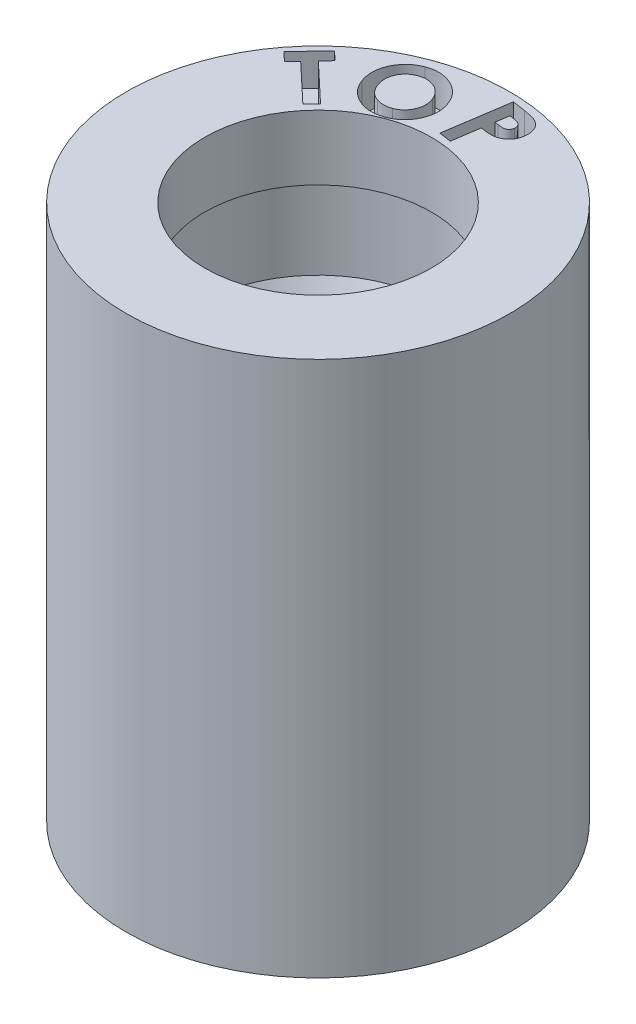
SolidWorks part; units mm, degrees
ref_plane "Front Plane" through (0, 0, 0) normal (0, 0, 1) x (1, 0, 0)
ref_plane "Top Plane" through (0, 0, 0) normal (0, 1, 0) x (1, 0, 0)
ref_plane "Right Plane" through (0, 0, 0) normal (1, 0, 0) x (0, 0, -1)
sketch "Sketch1" plane through (0, 0, 0) normal (0, 0, 1) x (1, 0, 0)
  line L0 (-5.9256, 16.5395) -> (-5.9256, 0)
  line L1 (-5.9256, 0) -> (-2.5, 0)
  line L2 (-2.5, 0) -> (-2.5, 1)
  line L3 (-2.5, 1) -> (-4.9256, 1) construction
  line L4 (-4.9256, 1) -> (-4.9256, 4) construction
  line L5 (-4.9256, 4) -> (-2.1655, 1.2398) construction
  line L6 (-2.1655, 1.2398) -> (-4.9256, 6.9535) construction
  line L7 (-4.9256, 6.9535) -> (-4.9256, 7.9535) construction
  line L8 (-4.9256, 7.9535) -> (-2.2655, 5.2933) construction
  line L9 (-2.2655, 5.2933) -> (-4.9256, 10.8) construction
  line L10 (-4.9256, 10.8) -> (-4.9256, 11.8) construction
  line L11 (-4.9256, 11.8) -> (-2.3655, 9.2398) construction
  line L12 (-4.9256, 7.9535) -> (-4.9256, 10.8) construction
  line L13 (-4.9256, 4) -> (-4.9256, 6.9535) construction
  line L14 (-2.3655, 9.2398) -> (-4.9256, 14.5395) construction
  line L15 (-4.9256, 14.5395) -> (-4.9256, 16.5395) construction
  line L16 (-3.1, 2.1744) -> (-3.1, 3.1744)
  line L17 (-3.2, 6.2279) -> (-3.2, 7.2279)
  line L18 (-3.3, 10.1744) -> (-3.3, 11.1744)
  line L19 (-3.3, 10.1744) -> (-4.9256, 11.8) construction
  line L20 (-4.9256, 11.8) -> (-4.9256, 14.5395) construction
  line L21 (-5.9256, 16.5395) -> (-4.9256, 16.5395)
  line L22 (-3.3, 11.1744) -> (-4.9256, 14.5395) construction
  line L23 (-4.9256, 7.9535) -> (-3.2, 6.2279) construction
  line L24 (-3.2, 7.2279) -> (-4.9256, 10.8) construction
  line L25 (-4.9256, 6.9535) -> (-3.1, 3.1744) construction
  line L26 (-3.1, 2.1744) -> (-4.9256, 4) construction
  line L27 (-3.3, 10.1744) -> (-3.8686, 8.612)
  line L28 (-3.8686, 8.612) -> (-3.2, 7.2279)
  line L29 (-3.2, 6.2279) -> (-3.7909, 4.6045)
  line L30 (-3.7909, 4.6045) -> (-3.1, 3.1744)
  line L31 (-3.1, 2.1744) -> (-3.5274, 1)
  line L32 (-3.5274, 1) -> (-2.5, 1)
  line L33 (-4.9256, 16.5395) -> (-3.5, 16.5395)
  line L34 (-3.5, 16.5395) -> (-3.5, 14.5395)
  line L35 (-3.5, 14.5395) -> (-4.9256, 14.5395) construction
  line L36 (-3.3, 11.1744) -> (-3.6937, 11.9894)
  line L37 (-3.6937, 11.9894) -> (-3.6937, 14.5395)
  line L38 (-3.6937, 14.5395) -> (-3.5, 14.5395)
  dimension "D3" = 1
  dimension "D2" = 45
  dimension "D4" = 45
  dimension "D5" = 45
  dimension "D1" = 1
  dimension "D9" = 2.5
  dimension "D10" = 1
  dimension "D6" = 3.3
  dimension "D7" = 3.2
  dimension "D8" = 3.1
  dimension "D11" = 1
  dimension "D12" = 3
  dimension "D13" = 2
  dimension "D14" = 200
  dimension "D15" = 3.5
ref_axis "Axis1" through (0, 31.7469, 0) along (0, -1, 0)
revolve "Revolve1" add sketch "Sketch1" angle 360 about axis through (0, 31.7469, 0) along (0, -1, 0)
sketch "Sketch2" plane through (0, 16.5395, 0) normal (0, 1, 0) x (1, 0, 0)
  arc A0 (-3.1309, 2.1162) -> (3.3228, 1.7999) centre (0, 0) cw construction
  text T0 "TOP" font "Century Gothic" height 2
extrude "Cut-Extrude1" cut sketch "Sketch2" against normal blind 1
equation "\"angle\"=45"
equation "\"D2@Sketch1\"=\"angle\""
equation "\"D4@Sketch1\"=\"angle\""
equation "\"D5@Sketch1\"=\"angle\""
